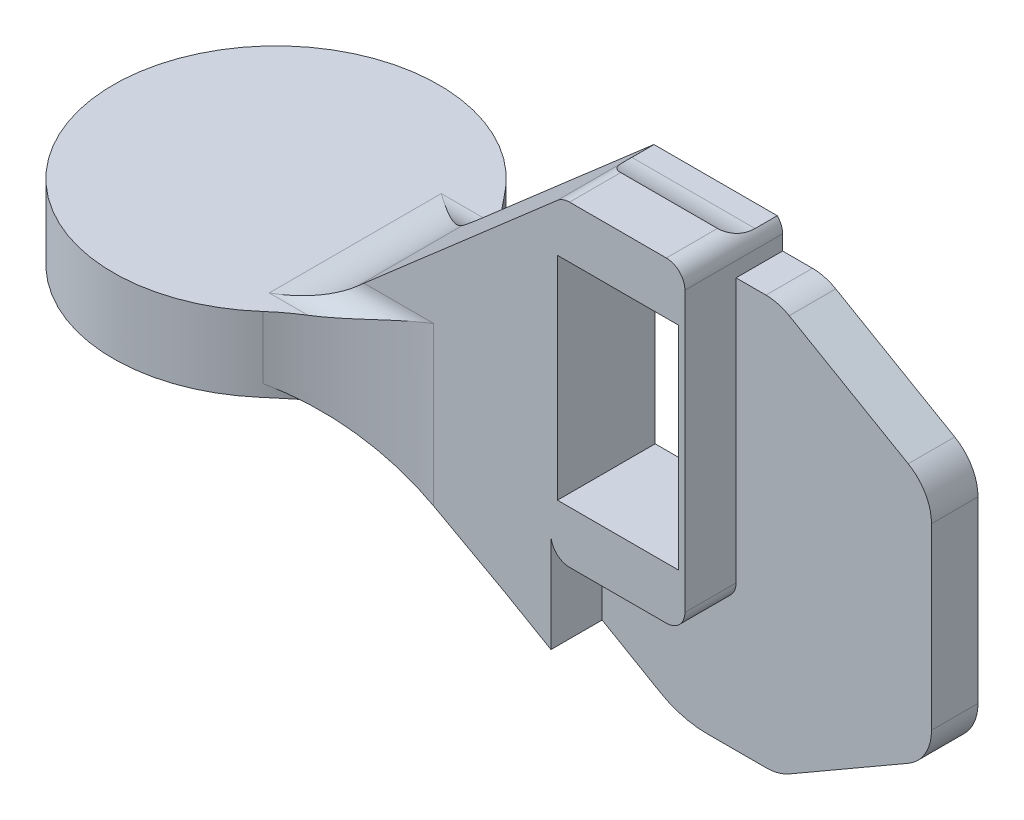
SolidWorks part; units mm, degrees
material "ABS"
ref_plane "Front Plane" through (0, 0, 0) normal (0, 0, 1) x (1, 0, 0)
ref_plane "Top Plane" through (0, 0, 0) normal (0, 1, 0) x (1, 0, 0)
ref_plane "Right Plane" through (0, 0, 0) normal (1, 0, 0) x (0, 0, -1)
other "Center of Mass"
sketch "Sketch1" plane through (0, 0, 0) normal (0, 1, 0) x (1, 0, 0)
  line L0 (0, 0) -> (128.1157, 0) construction
  line L2 (30, -2.5) -> (82.5, -2.5)
  line L4 (30, 2.5) -> (82.5, 2.5)
  line L5 (82.5, -2.5) -> (82.5, 2.5)
  arc A0 (14, 10.5) -> (14, -10.5) centre (0, 0) ccw
  arc A1 (30, 2.5) -> (14, 10.5) centre (30, 22.5) cw
  arc A2 (14, -10.5) -> (30, -2.5) centre (30, -22.5) cw
  point P3 (50, 0)
  dimension "D1" = 35
  dimension "D4" = 20
  dimension "D5" = 20
  dimension "D2" = 5
  dimension "D3" = 82.5
extrude "Boss-Extrude1" add sketch "Sketch1" along normal blind 8
sketch "Sketch4" plane through (82.5, 0, 0) normal (1, 0, 0) x (0, 0, -1)
  line L0 (0, 8) -> (0, 0) construction
  line L1 (-2.5, 8) -> (2.5, 8) construction
  line L3 (-2.5, -21) -> (2.5, -21)
  line L4 (-2.5, -21) -> (-2.5, 29)
  line L5 (-2.5, 29) -> (2.5, 29)
  line L6 (2.5, -21) -> (2.5, 29)
  line L7 (-2.5, -21) -> (2.5, 29) construction
  line L8 (-2.5, 29) -> (2.5, -21) construction
  point P5 (0, 4)
  dimension "D1" = 50
  dimension "D2" = 5
extrude "Boss-Extrude4" add sketch "Sketch4" against normal blind 50
sketch "Sketch5" plane through (0, 0, 2.5) normal (0, 0, 1) x (1, 0, 0)
  line L0 (82.5, 4) -> (30, 4) construction
  line L1 (82.5, 29) -> (82.5, -21) construction
  line L2 (30, 8) -> (30, 0) construction
  line L3 (57.5, 29) -> (57.5, -21) construction
  line L4 (32.5, 29) -> (82.5, 29) construction
  line L5 (32.5, -21) -> (82.5, -21) construction
  line L6 (56.25, 4) -> (30, 4) construction
  line L7 (32.5, 29) -> (32.5, 8) construction
  line L8 (32.5, 30.25) -> (57, 30.25)
  line L9 (32.5, 30.25) -> (32.5, -22.25)
  line L10 (32.5, -22.25) -> (57, -22.25)
  line L11 (57, 30.25) -> (57, -22.25)
  line L12 (32.5, 30.25) -> (57, -22.25) construction
  line L13 (32.5, -22.25) -> (57, 30.25) construction
  line L14 (44.75, -22.25) -> (44.75, 30.25) construction
  line L15 (38.25, 1.2) -> (51.25, 24) construction
  line L16 (38.25, 24) -> (51.25, 24)
  line L17 (38.25, 24) -> (38.25, 1.2)
  line L18 (38.25, 1.2) -> (51.25, 1.2)
  line L19 (51.25, 24) -> (51.25, 1.2)
  line L20 (38.25, 12.6) -> (51.25, 12.6) construction
  line L21 (51.95, -4.4) -> (37.55, -4.4)
  line L22 (51.95, -4.4) -> (51.95, 29.6)
  line L23 (51.95, 29.6) -> (37.55, 29.6)
  line L24 (37.55, -4.4) -> (37.55, 29.6)
  line L25 (51.95, -4.4) -> (37.55, 29.6) construction
  line L26 (51.95, 29.6) -> (37.55, -4.4) construction
  circle A0 centre (44.75, 18) radius 12.25
  circle A1 centre (44.75, -10) radius 12.25
  circle A2 centre (44.75, -10) radius 15.75
  circle A3 centre (64.9562, -1.2988) radius 1.5
  circle A4 centre (64.9562, -1.2988) radius 3
  circle A5 centre (64.9562, 9.2988) radius 3
  circle A6 centre (64.9562, 9.2988) radius 1.5
  circle A7 centre (44.75, -10) radius 1.5
  circle A8 centre (44.75, -10) radius 3
  point P13 (44.75, 4)
  point P30 (44.75, 12.6)
  dimension "D4" = 12.25
  dimension "D5" = 24.5
  dimension "D13" = 31.5
  dimension "D14" = 3
  dimension "D16" = 6
  dimension "D17" = 22
  dimension "D18" = 3
  dimension "D19" = 6
  dimension "D1" = 24.5
  dimension "D2" = 52.5
  dimension "D3" = 0
  dimension "D6" = 12.25
  dimension "D7" = 6
  dimension "D8" = 22.8
  dimension "D9" = 13
  dimension "D10" = 34
  dimension "D11" = 14.4
  dimension "D12" = 5.6
  dimension "D15" = 5.2988
sketch "Sketch6" plane through (0, 0, 2.5) normal (0, 0, 1) x (1, 0, 0)
  circle A0 centre (44.75, -10) radius 1.5
  dimension "D1" = 3
sketch "Sketch8" plane through (0, 0, 2.5) normal (0, 0, 1) x (1, 0, 0)
  line L0 (37.55, -4.4) -> (37.55, 29.6)
  line L1 (37.55, 29.6) -> (51.95, 29.6)
  line L2 (51.95, 29.6) -> (51.95, -4.4)
  line L3 (51.95, -4.4) -> (37.55, -4.4)
  dimension "D1" = 34
extrude "Boss-Extrude5" add sketch "Sketch8" along normal blind 5.5
sketch "Sketch9" plane through (0, 0, 8) normal (0, 0, 1) x (1, 0, 0)
  line L0 (38.25, 24) -> (51.25, 24)
  line L1 (51.25, 24) -> (51.25, 1.2)
  line L2 (51.25, 1.2) -> (38.25, 1.2)
  line L3 (38.25, 1.2) -> (38.25, 24)
extrude "Cut-Extrude2" cut sketch "Sketch9" against normal through all
fillet "Fillet2" radius 5 2 edges at (32.5, -21, 0) (32.5, 29, 0)
fillet "Fillet3" radius 2 4 edges at (51.95, -4.4, 5.25) (51.95, 29.6, 5.25) (37.55, 29.6, 5.25) (37.55, -4.4, 5.25)
fillet "Fillet4" radius 6 1 edges at (44.75, 29, 2.5)
sketch "Sketch14" plane through (0, 0, 2.5) normal (0, 0, 1) x (1, 0, 0)
  line L0 (72.9562, 29) -> (72.9562, -21)
  line L1 (82.5, -21) -> (28.5, -21)
  line L2 (82.5, -21) -> (82.5, -19.5)
  line L3 (56.5017, -18) -> (28.5, -18)
  line L4 (28.5, -21) -> (28.5, -18)
  line L5 (51.3783, 29) -> (82.5, 29) construction
  line L6 (56.5017, 26) -> (28.5, 26)
  line L7 (82.5, 4) -> (14, 4) construction
  line L8 (14, 8) -> (14, 0) construction
  line L9 (51.3055, 29) -> (29.6549, 16.5)
  line L10 (29.6549, 16.5) -> (29.6549, -8.5)
  line L11 (29.6549, -8.5) -> (51.3055, -21)
  line L12 (51.3055, -21) -> (72.9562, -8.5)
  line L13 (72.9562, -8.5) -> (72.9562, 16.5)
  line L14 (72.9562, 16.5) -> (51.3055, 29)
  circle A0 centre (51.3055, 4) radius 21.6506 construction
  circle A1 centre (64.9562, 9.2988) radius 3 construction
  dimension "D4" = 8
  dimension "D6" = 25
  dimension "D1" = 3
  dimension "D2" = 8
  dimension "D3" = 54
  dimension "D5" = 0
extrude "Cut-Extrude6" cut sketch "Sketch14" against normal blind 10
fillet "Fillet5" radius 5 4 edges at (56.5017, 26, 0) (72.9562, 16.5, 0) (72.9562, -8.5, 0) (56.5017, -18, 0)
fillet "Fillet6" radius 10 1 edges at (46.1094, -18, 0)
ref_plane "Plane5" through (0, 0, 0) normal (0, 0, 1) x (1, 0, 0)
sketch "Sketch15" plane through (0, 0, 0) normal (0, 0, 1) x (1, 0, 0)
  line L0 (14, 8) -> (14, 0)
  line L1 (37.55, 8) -> (37.55, 0)
  line L2 (37.55, 21.0582) -> (37.55, -2.4) construction
  line L3 (37.55, 21.0582) -> (37.55, 27.6)
  line L4 (37.55, 27.6) -> (38.1358, 29.0142)
  line L5 (38.1358, 29.0142) -> (14, 8)
  line L7 (32.5, -10.1426) -> (14, 0)
  line L9 (37.55, 8) -> (37.55, 21.0582)
  line L11 (37.55, 0) -> (37.55, -13.0582)
  line L12 (32.5, -10.1426) -> (43.7889, -16.6603) construction
  line L13 (37.55, -13.0582) -> (32.5, -10.1426)
  arc A0 (39.55, 29.6) -> (37.55, 27.6) centre (39.55, 27.6) ccw construction
extrude "Boss-Extrude6" add sketch "Sketch15" along normal blind 8 and the other way blind 2.5
fillet "Fillet7" radius 5 1 edges at (22, 8, -2.5)
fillet "Fillet8" radius 5 1 edges at (22, 0, -2.5)
fillet "Fillet10" radius 20 1 edges at (16.225, 4, 8)
fillet "Fillet15" radius 3 1 edges at (19.4725, 8, 8)
fillet "Fillet16" radius 10 2 edges at (14, 8, 1.75) (14, 0, 1.5)
